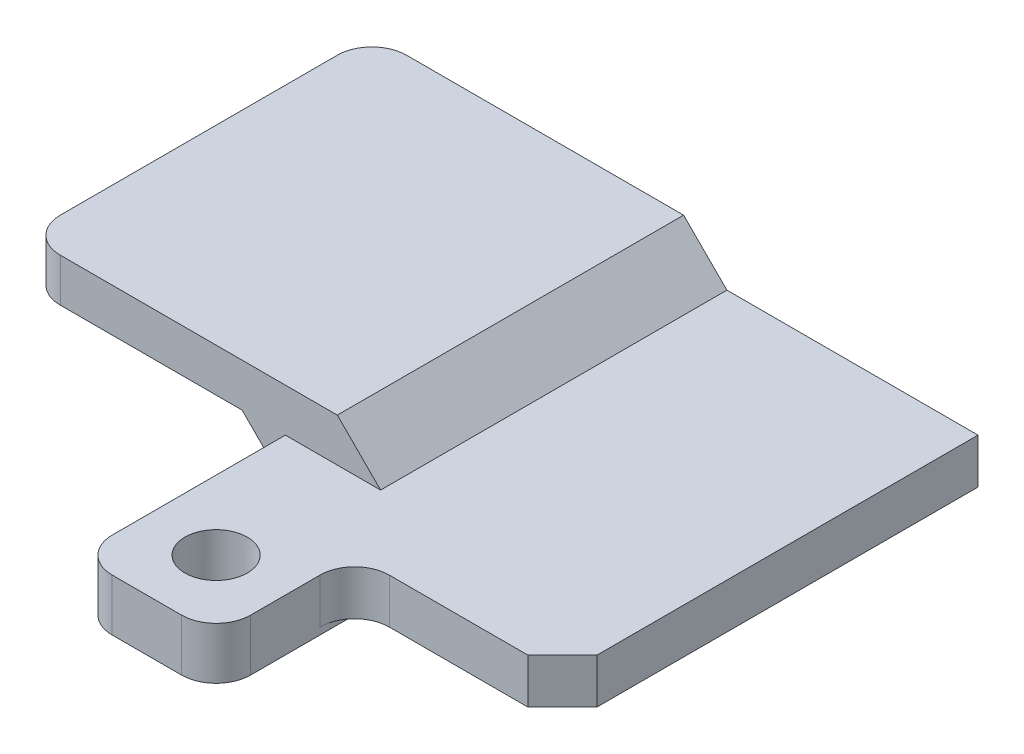
SolidWorks part; units mm, degrees
ref_plane "Płaszczyzna przednia" through (0, 0, 0) normal (0, 0, 1) x (1, 0, 0)
ref_plane "Płaszczyzna górna" through (0, 0, 0) normal (0, 1, 0) x (1, 0, 0)
ref_plane "Płaszczyzna prawa" through (0, 0, 0) normal (1, 0, 0) x (0, 0, -1)
sketch "Sketch1" plane through (0, 0, 0) normal (0, 1, 0) x (1, 0, 0)
  line L1 (0, 0) -> (20, 0)
  line L2 (0, 0) -> (0, 24)
  line L3 (0, 24) -> (20, 24)
  line L4 (20, 0) -> (20, 24)
  dimension "D1" = 24
  dimension "D2" = 20
extrude "Boss-Extrude1" add sketch "Sketch1" along normal blind 3
sketch "Sketch2" plane through (0, 3, 0) normal (0, 1, 0) x (1, 0, 0)
  line L0 (0, 24) -> (0, 0) construction
  line L1 (0, -8) -> (8, -8)
  line L2 (0, -8) -> (0, 0)
  line L3 (0, 0) -> (8, 0)
  line L4 (8, -8) -> (8, 0)
  line L5 (0, -8) -> (8, 0) construction
  line L6 (0, 0) -> (8, -8) construction
  line L7 (0, 0) -> (20, 0) construction
  circle A0 centre (4, -4) radius 1.8
  point P0 (4, -4)
  dimension "D2" = 3.6
  dimension "D1" = 8
extrude "Boss-Extrude2" add sketch "Sketch2" against normal up to surface (3 mm away) up to face at (10, 0, -12)
fillet "Fillet1" radius 2 3 edges at (8, 1.5, 0) (8, 1.5, 8) (0, 1.5, 8)
chamfer "Chamfer1" distance 2 angle 45 1 edges at (20, 1.5, 0)
sketch "Sketch3" plane through (0, 3, 0) normal (0, 1, 0) x (1, 0, 0)
  line L0 (20, 24) -> (0, 24) construction
  line L1 (3, 24) -> (-15, 24)
  line L2 (3, 24) -> (3, 0)
  line L3 (3, 0) -> (-15, 0)
  line L4 (-15, 24) -> (-15, 0)
  line L5 (10, 0) -> (18, 0) construction
  line L6 (0, 24) -> (0, -6) construction
  dimension "D1" = 18
  dimension "D2" = 3
extrude "Boss-Extrude3" add sketch "Sketch3" along normal blind 2.5
chamfer "Chamfer2" distance 2.5 angle 45 2 edges at (0, 3, -12) (3, 3, -12)
sketch "Sketch5" plane through (0, 0, 0) normal (0, 0, 1) x (1, 0, 0)
  line L7 (-15, 3) -> (-2.5, 3)
  line L8 (-2.5, 3) -> (0, 0.5)
  line L9 (0, 0.5) -> (0, 3)
  line L10 (0, 3) -> (5.5, 3)
  line L11 (5.5, 3) -> (3, 5.5)
  line L12 (3, 5.5) -> (-15, 5.5)
  line L13 (-15, 5.5) -> (-15, 3)
  line L14 (-15, 3) -> (-2.5, 3)
  line L15 (-2.5, 3) -> (0, 0.5)
  line L16 (0, 0.5) -> (0, 3)
  line L17 (0, 3) -> (5.5, 3)
  line L18 (5.5, 3) -> (3, 5.5)
  line L19 (3, 5.5) -> (-15, 5.5)
  line L20 (-15, 5.5) -> (-15, 3)
  dimension "D1" = 0
extrude "Cut-Extrude4" cut sketch "Sketch5" against normal blind 4
fillet "Fillet2" radius 2 2 edges at (-15, 4.25, -24) (-15, 4.25, -4)
sketch "Sketch4" plane through (0, 0, 0) normal (0, -1, 0) x (1, 0, 0)
  line L0 (8, 2) -> (8, 0)
  line L1 (0, 0) -> (8, 0)
  line L2 (0, 0) -> (0, -24)
  line L3 (0, -24) -> (20, -24)
  line L4 (20, 0) -> (20, -24)
  line L5 (8, 2) -> (20, 2)
  line L6 (20, 2) -> (20, 0)
  point P10 (0, 0)
  line M1 (20, -24) -> (20, -2)
  line M2 (20, -2) -> (18, 0)
  line M3 (18, 0) -> (10, 0)
  line M9 (0, 6) -> (0, -24)
  line M10 (0, -24) -> (20, -24)
extrude "Cut-Extrude3" cut sketch "Sketch4" against normal blind 0.4 contours L1 M9 M10 M1 M2 M3 region at (10.1905, 0, -11.381)
